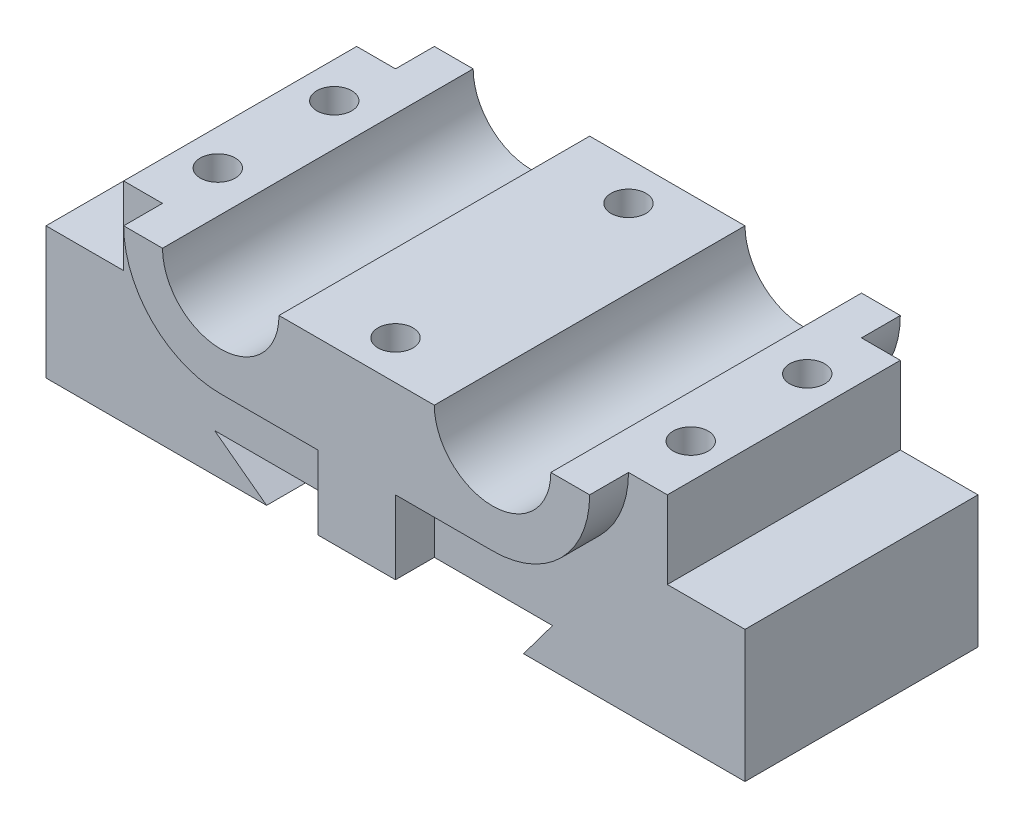
SolidWorks part; units mm, degrees
ref_plane "Front Plane" through (0, 0, 0) normal (0, 0, 1) x (1, 0, 0)
ref_plane "Top Plane" through (0, 0, 0) normal (0, 1, 0) x (1, 0, 0)
ref_plane "Right Plane" through (0, 0, 0) normal (1, 0, 0) x (0, 0, -1)
sketch "Sketch1" plane through (0, 0, 0) normal (0, 0, 1) x (1, 0, 0)
  line L0 (0, 0) -> (0, 16.9736)
  line L1 (0, 16.9736) -> (10, 16.9736)
  line L2 (10, 16.9736) -> (10, 26.9736)
  line L3 (10, 26.9736) -> (20, 26.9736)
  line L4 (35, 26.9736) -> (55, 26.9736)
  line L5 (70, 26.9736) -> (80, 26.9736)
  line L6 (80, 26.9736) -> (80, 16.9736)
  line L7 (80, 16.9736) -> (90, 16.9736)
  line L8 (90, 16.9736) -> (90, 0)
  line L9 (90, 0) -> (61.4868, 0)
  line L10 (61.4868, 0) -> (65.2193, 5)
  line L11 (65.2193, 5) -> (21.7073, 5)
  line L12 (21.7073, 5) -> (28.4052, 0)
  line L13 (28.4052, 0) -> (0, 0)
  line L14 (27.5, 14.4736) -> (40, 14.4736)
  line L15 (40, 14.4736) -> (40, 5)
  line L16 (62.5, 14.4736) -> (50, 14.4736)
  line L17 (50, 14.4736) -> (50, 5)
  arc A0 (20, 26.9736) -> (35, 26.9736) centre (27.5, 26.9736) ccw
  arc A1 (55, 26.9736) -> (70, 26.9736) centre (62.5, 26.9736) ccw
  arc A2 (15, 26.9736) -> (27.5, 14.4736) centre (27.5, 26.9736) ccw
  arc A3 (62.5, 14.4736) -> (75, 26.9736) centre (62.5, 26.9736) ccw
  point P14 (27.5, 19.4736)
  point P20 (62.5, 19.4736)
  dimension "D8" = 7.5
  dimension "D9" = 7.5
  dimension "D10" = 12.5
  dimension "D11" = 12.5
  dimension "D1" = 90
  dimension "D2" = 35
  dimension "D3" = 17.5
  dimension "D4" = 17.5
  dimension "D5" = 10
  dimension "D6" = 10
  dimension "D7" = 5
  dimension "D12" = 15
extrude "Boss-Extrude1" add sketch "Sketch1" along normal mid plane 30 contours A2 L3 L2 L1 L0 L13 L12 L11 L15 L14 | A3 L16 L17 L11 L10 L9 L8 L7 L6 L5 region at (17.05, 10.0058, 0) region at (72.8497, 9.9213, 0)
extrude "Boss-Extrude2" add sketch "Sketch1<3>" along normal mid plane 40 contours L16 A3 L5 A1 L4 A0 L3 A2 L14 L15 L11 L17 region at (45, 18.4756, 0)
sketch "Sketch1<3>" plane through (0, 0, 0) normal (0, 0, 1) x (1, 0, 0) same geometry as "Sketch1"
sketch "Sketch2" plane through (0, 26.9736, 0) normal (0, 1, 0) x (1, 0, 0)
  line L0 (0, 0) -> (90, 0) construction
  line L1 (90, -15) -> (90, 15) construction
  line L2 (35, 20) -> (55, 20) construction
  line L3 (35, -20) -> (55, -20) construction
  circle A0 centre (14.6173, 7.5) radius 2.25
  circle A1 centre (45, 15) radius 2.25
  circle A4 centre (45, -15) radius 2.25
  circle A5 centre (14.6173, -7.5) radius 2.25
  circle A6 centre (75.5114, 7.5) radius 2.25
  circle A7 centre (75.5114, -7.5) radius 2.25
  point P19 (45, 20)
  dimension "D1" = 4.5
  dimension "D2" = 4.5
  dimension "D3" = 4.5
  dimension "D5" = 4.5
  dimension "D4" = 15
  dimension "D6" = 5
  dimension "D7" = 5
  dimension "D8" = 15
extrude "Cut-Extrude2" cut sketch "Sketch2" against normal blind 12.5
